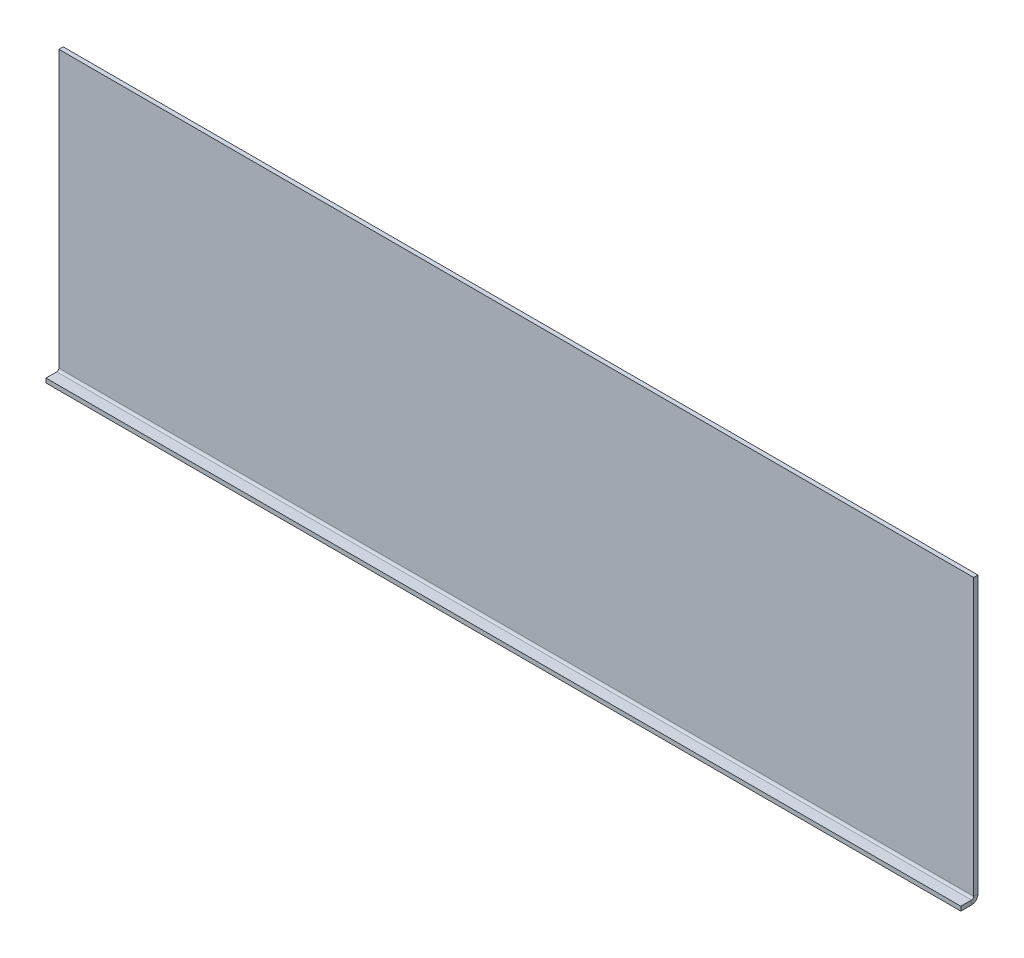
SolidWorks part; units mm, degrees
note: The reader was unsure of these and kept them because the rebuilt part matched: flange length of "Edge-Flange1".
material "6061-T6 (SS)"
ref_plane "X-Y Datum" through (0, 0, 0) normal (0, 0, 1) x (1, 0, 0)
ref_plane "X-Z Datum" through (0, 0, 0) normal (0, 1, 0) x (1, 0, 0)
ref_plane "Y-Z Datum" through (0, 0, 0) normal (1, 0, 0) x (0, 0, -1)
sketch "Sketch1" plane through (0, 0, 0) normal (0, 0, 1) x (1, 0, 0)
  line L0 (676.402, 3.175) -> (676.402, 0) construction
  line L5 (0, 0) -> (676.402, 0)
  line L6 (0, 0) -> (0, 204.155)
  line L7 (0, 204.155) -> (676.402, 204.155)
  line L8 (676.402, 0) -> (676.402, 204.155)
  line L9 (449.7984, 204.155) -> (452.9734, 204.155) construction
base flange "Base-Flange1" sketch "Sketch1" thickness 3.175 reverse thickness direction no parameters "D1"=1.5875
edge flange "Edge-Flange1" sketch "Sketch8" flange angle 90 flange length 12.7 flange position bend outside bend radius 1.5875 thickness 3.175 relief rectangular parameters "D6"=10
sketch "Sketch8" plane through (0, 0, 0) normal (0, 1, 0) x (-1, 0, 0)
  line L2 (-676.402, 0) -> (-676.402, 9.525)
  line L3 (-676.402, 9.525) -> (0, 9.525)
  line L4 (0, 9.525) -> (0, 0)
  line L5 (0, 0) -> (-676.402, 0) construction
  line L6 (0, 0) -> (-676.402, 0)
bend "EdgeBend1" bend radius 1.5875 bend angle 90 parameters "D5"=1
sketch "Sketch9" plane through (0, 0, 1.251) normal (0, 0, -1) x (-1, 0, 0)
  circle A0 centre (-267.5089, 43.7323) radius 9.525
  circle A1 centre (-180.1763, 43.7323) radius 9.525
  circle A2 centre (-38.9089, 43.7323) radius 9.525
  circle A3 centre (-637.3763, 43.7323) radius 9.525
  circle A4 centre (-496.1089, 43.7323) radius 9.525
  circle A5 centre (-408.7763, 43.7323) radius 9.525
  circle A6 centre (-38.9089, 163.5978) radius 9.525
  circle A7 centre (-180.1763, 163.5978) radius 9.525
  circle A8 centre (-408.7763, 163.5978) radius 9.525
  circle A9 centre (-267.5089, 163.5978) radius 9.525
  circle A10 centre (-637.3763, 163.5978) radius 9.525
  circle A11 centre (-496.1089, 163.5978) radius 9.525
  point P0 (-408.7763, 43.7323)
  point P1 (-267.5089, 43.7323)
  point P3 (-637.3763, 43.7323)
  point P5 (-496.1089, 43.7323)
  point P7 (-180.1763, 43.7323)
  point P9 (-38.9089, 43.7323)
  point P26 (-637.3763, 163.5978)
  point P27 (-496.1089, 163.5978)
  point P29 (-408.7763, 163.5978)
  point P31 (-267.5089, 163.5978)
  point P33 (-180.1763, 163.5978)
  point P35 (-38.9089, 163.5978)
  dimension "D1" = 19.05
extrude "Cut-Extrude1" cut sketch "Sketch9" against normal blind 3.175
sketch "Bend-Lines1" [suppressed] plane through (0, 0, 0) normal (0, 1, 0) x (1, 0, 0)
sketch "Bounding-Box1" [suppressed] plane through (0, 0, 0) normal (0, 1, 0) x (1, 0, 0)
sheet metal parameters "Sheet-Metal2" thickness 3.175 parameters "D1"=1.5875
flat pattern "Flat-Pattern2" [suppressed]
sketch "Bend-Lines2" plane through (0, 0, 0) normal (0, 1, 0) x (1, 0, 0)
sketch3d "Bounding-Box2" [suppressed]
  line L0 (0, 0, 0) -> (676.402, 0, 0) construction
  line L1 (0, 204.155, 0) -> (676.402, 204.155, 0) construction
  line L2 (0, 0, 0) -> (0, 204.155, 0) construction
  line L3 (676.402, 0, 0) -> (676.402, 204.155, 0) construction
sheet metal parameters "Sheet-Metal3" thickness 3.175 parameters "D1"=1.5875
flat pattern "Flat-Pattern2"
sketch "Bend-Lines2" plane through (0, 0, 0) normal (0, 0, 1) x (1, 0, 0)
  line L0 (0, -2.4936) -> (676.402, -2.4936) construction
  line L1 (0, -2.4936) -> (676.402, -2.4936) construction
sketch3d "Bounding-Box2" [suppressed]
  line L0 (0, -12.9248, 0) -> (676.402, -12.9248, 0) construction
  line L1 (0, 204.155, 0) -> (676.402, 204.155, 0) construction
  line L2 (0, -12.9248, 0) -> (0, 204.155, 0) construction
  line L3 (676.402, -12.9248, 0) -> (676.402, 204.155, 0) construction
bend of the flat pattern "Flatten-<EdgeBend1>1"
sheet metal parameters "Sheet-Metal4" thickness 3.175 parameters "D1"=1.5875
flat pattern "Flat-Pattern2"
sketch "Bend-Lines2" plane through (0, 0, 0) normal (0, 0, 1) x (1, 0, 0)
  line L0 (0, -2.4936) -> (676.402, -2.4936) construction
  line L1 (0, -2.4936) -> (676.402, -2.4936) construction
sketch3d "Bounding-Box2" [suppressed]
  line L0 (0, -12.9248, 0) -> (676.402, -12.9248, 0) construction
  line L1 (0, 204.155, 0) -> (676.402, 204.155, 0) construction
  line L2 (0, -12.9248, 0) -> (0, 204.155, 0) construction
  line L3 (676.402, -12.9248, 0) -> (676.402, 204.155, 0) construction
bend of the flat pattern "Flatten-<EdgeBend1>1"
